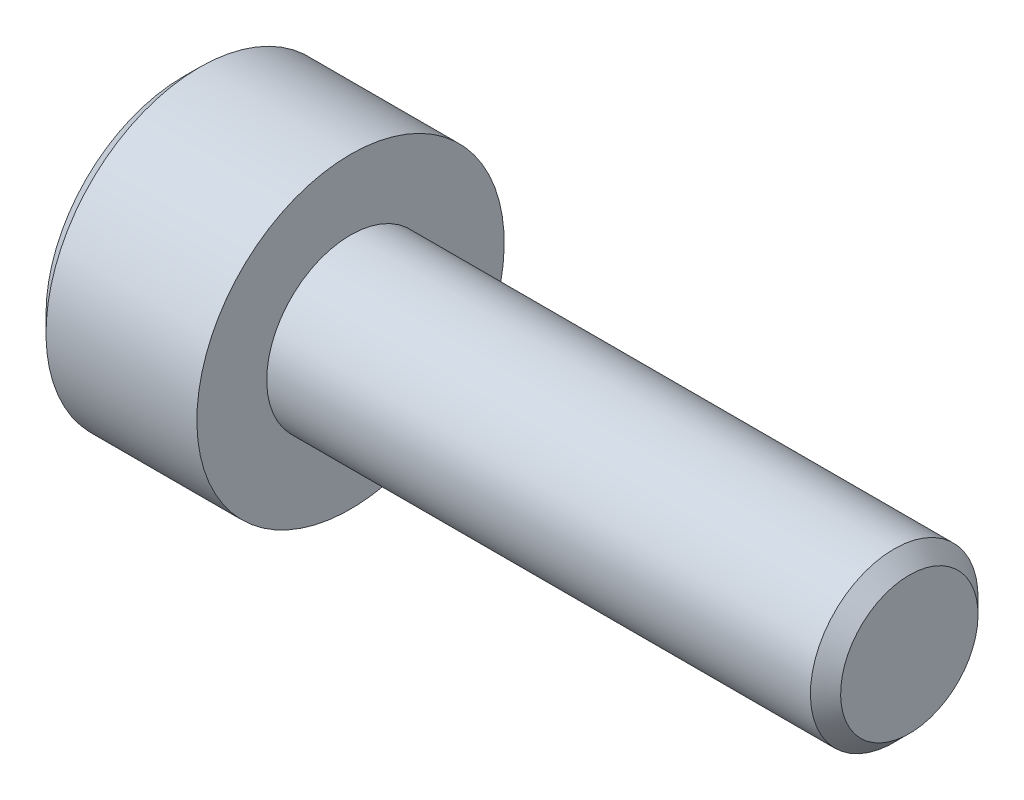
SolidWorks part; units mm, degrees
ref_plane "Front Plane" through (0, 0, 0) normal (0, 0, 1) x (1, 0, 0)
ref_plane "Top Plane" through (0, 0, 0) normal (0, 1, 0) x (1, 0, 0)
ref_plane "Right Plane" through (0, 0, 0) normal (1, 0, 0) x (0, 0, -1)
ref_axis "Axis_X" through (-3.65, 0, 0) along (1, 0, 0)
ref_axis "Axis_Y" through (0, 3.025, 0) along (0, -1, 0)
ref_axis "Axis_Z" through (0, 0, -3.025) along (0, 0, 1)
sketch "Sketch1" plane through (0, 0, 0) normal (0, 0, 1) x (1, 0, 0)
  line L0 (-4.1583, 0) -> (10, 0) construction
  line L1 (0, 1.5) -> (0, 2.75)
  line L2 (-3, 0) -> (-3, 2.45)
  line L3 (0, 1.5) -> (9.7295, 1.5)
  line L4 (9.7295, 1.5) -> (10, 1.2295)
  line L5 (10, 1.2295) -> (10, 0)
  line L6 (10, 0) -> (-3, 0)
  line L7 (-2.7, 2.75) -> (0, 2.75)
  line L8 (9.7295, -1.5) -> (10, -1.2295) construction
  line L9 (3.025, 0) -> (-3.025, 0) construction
  line L10 (-3, 2.45) -> (-2.7, 2.75)
  line L11 (-3, -2.45) -> (-2.7, -2.75) construction
  line L12 (0, -3.025) -> (0, 3.025) construction
  dimension "FIX_1" = 45
  dimension "M" = 3
  dimension "ATD_1" = 2.459
  dimension "L" = 10
  dimension "E" = 3
  dimension "A" = 5.5
revolve "Revolve1" add sketch "Sketch1" angle 360 about L6
sketch "Sketch2" plane through (-3, 0, 0) normal (-1, 0, 0) x (0, 0, 1)
  line L0 (0, -3.025) -> (0, 3.025) construction
  line L1 (0, 1.4434) -> (-1.25, 0.7217)
  line L2 (-1.25, 0.7217) -> (-1.25, -0.7217)
  line L3 (-1.25, -0.7217) -> (0, -1.4434)
  line L4 (0, -1.4434) -> (1.25, -0.7217)
  line L5 (1.25, -0.7217) -> (1.25, 0.7217)
  line L6 (1.25, 0.7217) -> (0, 1.4434)
  circle A0 centre (0, 0) radius 1.25 construction
  dimension "B" = 2.5
extrude "Cut-Extrude1" cut sketch "Sketch2" against normal blind 1.5
equation "\"Factor\"= 1.082532"
equation "\"Pitch\"= IIF ( \"M\" = 30 , 3.5 , IIF ( \"M\" = 24 , 3 , IIF ( \"M\" = 20 , 2.5 , IIF ( \"M\" = 16 , 2 , IIF ( \"M\" = 14 , 2 , IIF ( \"M\" = 12 , 1.75 , IIF ( \"M\" = 10 , 1.5 , IIF ( \"M\" = 8 , 1.25 , IIF ( \"M\" = 6 , 1 , IIF ( \"M\" = 5 , 0.8 , IIF ( \"M\" = 4 , 0.7 , IIF ( \"M\" = 3 , 0.5 , IIF ( \"M\" = 2.5 , 0.45 , 0.4 ) ) ) ) ) ) ) ) ) ) ) ) )"
equation "\"ATD_1\"= round ( \"M\" - \"Factor\" * \"Pitch\" , 3 )"
equation "\"L_s\"= IIF ( ( \"M\" = 12 and \"L\" > 50 ) , 36 , IIF ( ( \"M\" = 12 and \"L\" = < 50 ) , \"L\" , IIF ( ( \"M\" = 10 and \"L\" > 40 ) , 32 , IIF ( ( \"M\" = 10 and \"L\" = < 40 ) , \"L\" , IIF ( ( \"M\" = 8 and \"L\" > 35 ) , 28 , IIF ( ( \"M\" = 8 and \"L\" = < 35 ) , \"L\" , IIF ( ( \"M\" = 6 and \"L\" > 30 ) , 24 , IIF ( ( \"M\" = 6 and \"L\" = < 30 ) , \"L\" , IIF ( ( \"M\" = 5 and \"L\" > 25 ) , 22 , IIF ( ( \"M\" = 5 and \"L\" = < 25 ) , \"L\" , IIF ( ( \"M\" = 4 and \"L\" > 25 ) , 20 , IIF ( ( \"M\" = 4 and \"L\" = < 25 ) , \"L\" , IIF ( ( \"M\" = 3 and \"L\" > 20 ) , 18 , \"L\" ) ) ) ) ) ) ) ) ) ) ) ) )"
equation "\"E\"= \"M\""
equation "\"A\"= IIF ( \"M\" = 12 , 18 , IIF ( \"M\" = 10 , 16 , IIF ( \"M\" = 8 , 13 , IIF ( \"M\" = 6 , 10 , IIF ( \"M\" = 5 , 8.5 , IIF ( \"M\" = 4 , 7 , 5.5 ) ) ) ) ) )"
equation "\"B\"= IIF ( \"M\" = 12 , 10 , IIF ( \"M\" = 10 , 8 , IIF ( \"M\" = 8 , 6 , IIF ( \"M\" = 6 , 5 , IIF ( \"M\" = 5 , 4 , IIF ( \"M\" = 4 , 3 , 2.5 ) ) ) ) ) )"
equation "\"KSS_1\"= \"M\" / 10"
equation "\"KSS_2\"= \"M\" / 2"
